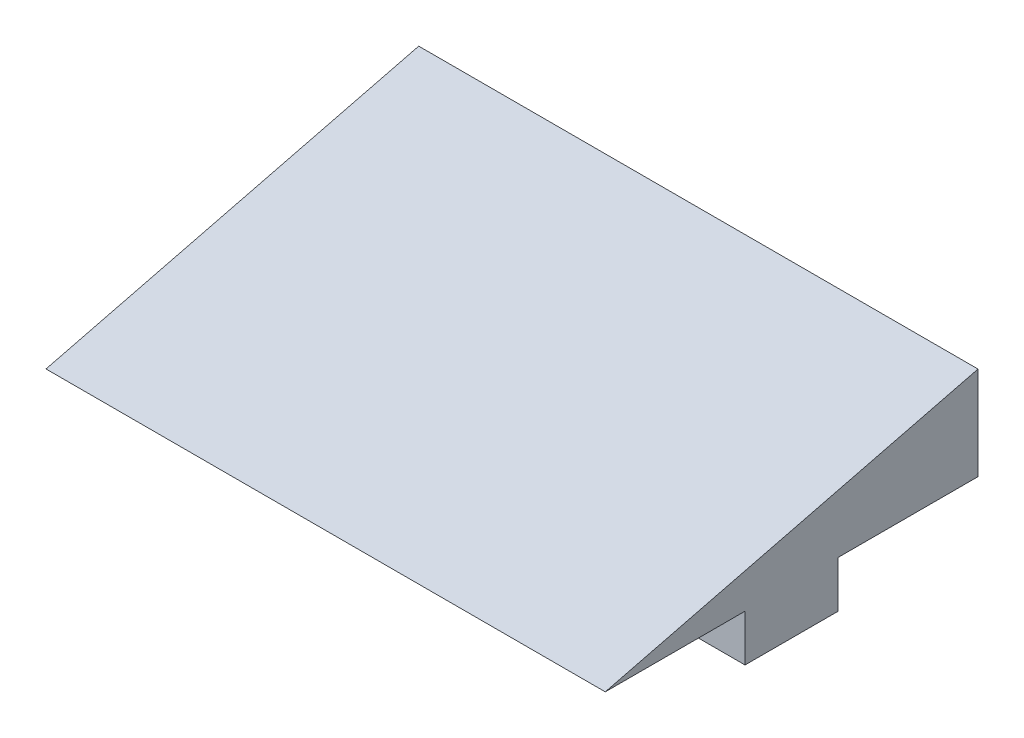
SolidWorks part; units mm, degrees
ref_plane "Front Plane" through (0, 0, 0) normal (0, 0, 1) x (1, 0, 0)
ref_plane "Top Plane" through (0, 0, 0) normal (0, 1, 0) x (1, 0, 0)
ref_plane "Right Plane" through (0, 0, 0) normal (1, 0, 0) x (0, 0, -1)
sketch "Sketch3" plane through (0, 0, 0) normal (0, 1, 0) x (1, 0, 0)
  line L1 (-60, 40) -> (60, 40)
  line L2 (-60, 40) -> (-60, -40)
  line L3 (-60, -40) -> (60, -40)
  line L4 (60, 40) -> (60, -40)
  line L5 (-60, 40) -> (60, -40) construction
  line L6 (-60, -40) -> (60, 40) construction
  point P0 (0, 0)
  dimension "D1" = 120
  dimension "D2" = 80
extrude "Boss-Extrude1" add sketch "Sketch3" along normal blind 20
sketch "Sketch4" plane through (60, 0, 0) normal (1, 0, 0) x (0, 0, -1)
  line L2 (-40, 0) -> (40, 0)
  line L3 (-39.9714, 0) -> (40, 20)
  line L4 (-38.6975, 0) -> (40, 0)
  line M4 (-40, 0) -> (40, 0)
  line M6 (40, 20) -> (-40, 20)
  line M7 (-40, 20) -> (-40, 0)
extrude "Cut-Extrude3" cut sketch "Sketch4" against normal blind 120 and the other way through all contours L3 M4 M6 M7 region at (60, 13.3309, 13.3333)
sketch "Sketch5" plane through (60, 0, 0) normal (1, 0, 0) x (0, 0, -1)
  line L0 (-9.9857, 0) -> (-9.9857, -10)
  line L1 (-39.9714, 0) -> (40, 0) construction
  line L2 (-9.9857, -10) -> (10.0143, -10)
  line L3 (10.0143, -10) -> (10.0143, 0)
  line L4 (-39.9714, 0) -> (-9.9857, 0)
  line L5 (-9.9857, 0) -> (10.0143, 0)
  line L7 (40, 20) -> (-39.9714, 0)
  line L8 (-39.9714, 0) -> (40, 0)
  line L9 (40, 0) -> (40, 20)
  line L10 (40, 20) -> (-39.9714, 0)
  line L11 (10.0143, 0) -> (40, 0)
  line L12 (40, 0) -> (40, 20)
  point P4 (0.0143, 0)
  line M4 (-39.9714, 0) -> (40, 0)
  dimension "D1" = 10
  dimension "D2" = 20
  dimension "D3" = 10
  dimension "D4" = 0
extrude "Boss-Extrude2" add sketch "Sketch5" against normal blind 120 contours L2 L3 L0 M4 region at (60, -5, -0.0143)
